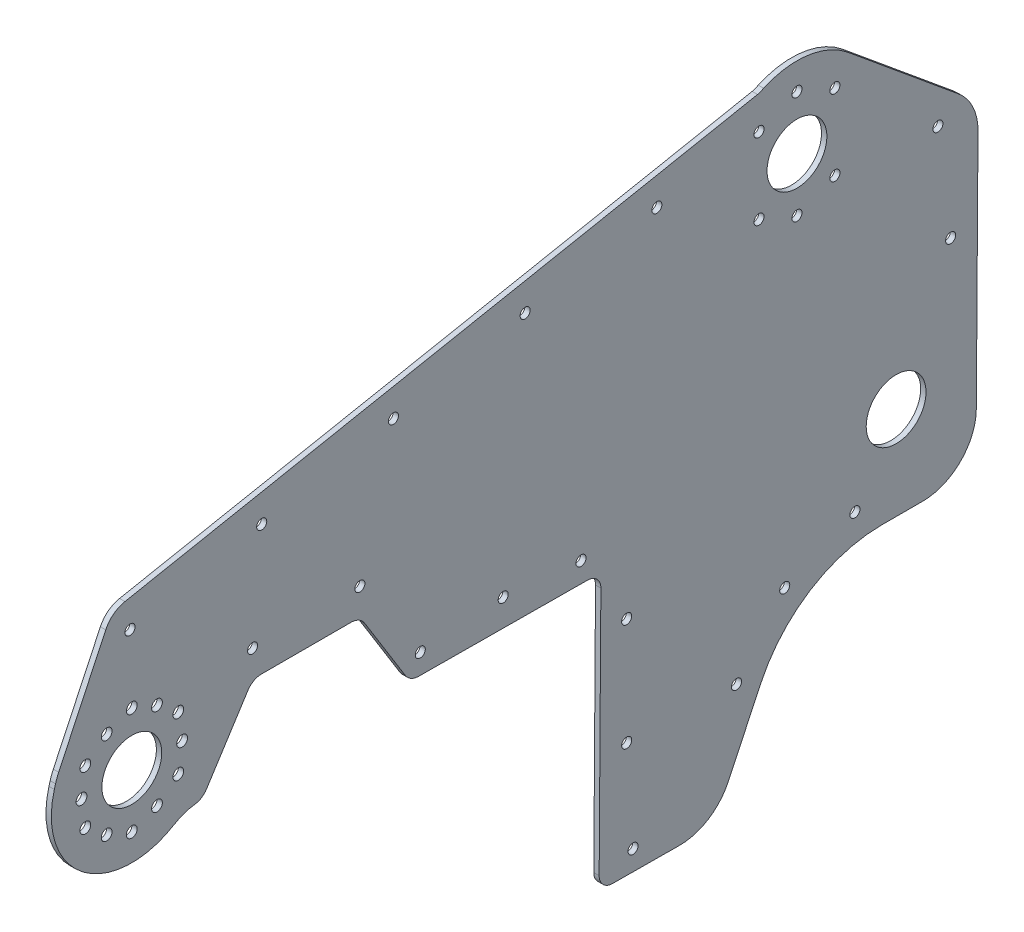
SolidWorks part; units mm, degrees
ref_plane "Front Plane" through (0, 0, 0) normal (0, 0, 1) x (1, 0, 0)
ref_plane "Top Plane" through (0, 0, 0) normal (0, 1, 0) x (1, 0, 0)
ref_plane "Right Plane" through (0, 0, 0) normal (1, 0, 0) x (0, 0, -1)
sketch "Sketch1" plane through (2085.2745, 0, 0) normal (-1, 0, 0) x (0, 0, 1)
  line L0 (-470.4626, 294.284) -> (-813.3543, 291.9025) construction
  line L1 (-819.6601, 285.5085) -> (-816.3083, -197.0799) construction
  line L2 (-816.3083, -197.0799) -> (-644.8624, -195.8891) construction
  line L3 (-638.5567, -189.4951) -> (-639.3726, -72.023) construction
  line L4 (-633.0668, -65.629) -> (-442.3722, -64.3046) construction
  line L5 (-380.6906, -25.2502) -> (-470.4626, 294.284) construction
  line L6 (-470.4626, 294.284) -> (-813.3543, 291.9025) construction
  line L7 (-819.6601, 285.5085) -> (-818.6898, 145.8119) construction
  line L8 (-676.4765, -196.1087) -> (-644.8624, -195.8891)
  line L9 (-638.5567, -189.4951) -> (-639.3726, -72.023)
  line L10 (-633.0668, -65.629) -> (-553.1901, -65.0743)
  line L11 (-380.6906, -25.2502) -> (-381.2742, -23.1727)
  line L12 (-406.6004, 23.1935) -> (-802.249, 140.9199) construction
  line L14 (-756.4363, 89.0125) -> (-808.6343, 45.9004)
  line L15 (-817.8587, 26.1401) -> (-817.0703, -87.3715)
  line L16 (-818.5707, 128.6591) -> (-817.9425, 38.2125) construction
  line L17 (-393.1787, 19.1998) -> (-470.4626, 294.284) construction
  line L18 (-699.6149, -181.5678) -> (-715.0401, -148.9488)
  line L19 (-772.4451, -112.5951) -> (-791.6709, -112.5951)
  line L20 (-816.8951, -112.5951) -> (-816.3083, -197.0799) construction
  line L21 (-816.3083, -197.0799) -> (-692.6854, -196.2212) construction
  line L22 (-530.97, 35.9025) -> (-713.5248, 93.2198) construction
  line L23 (-384.9948, -9.9298) -> (-389.3911, 5.7185) construction
  line L24 (-546.7673, -61.4706) -> (-527.5902, -30.5489)
  line L25 (-521.1144, -26.945) -> (-478.7266, -26.945)
  line L26 (-472.3074, -30.4591) -> (-452.7015, -61.1107)
  line L27 (-405.0283, 28.0353) -> (-382.753, -19.2109)
  line L28 (-475.9205, -39.5052) -> (-523.9205, -39.5052) construction
  line L29 (-475.9205, -39.5052) -> (-523.9205, -39.5052) construction
  line L30 (-548.9841, -65.045) -> (-450.6219, -64.3619) construction
  line L31 (-527.1657, 35.3193) -> (-416.5156, 35.3193) construction
  line L32 (-398.1188, -5.8092) -> (-529.1126, 35.3193) construction
  line L33 (-713.5248, 93.2198) -> (-414.0951, 35.0865)
  line L34 (-792.0032, 59.6366) -> (-540.5464, 59.6366) construction
  arc A0 (-813.3543, 291.9025) -> (-819.6601, 285.5085) centre (-813.3102, 285.5526) ccw construction
  arc A1 (-644.8624, -195.8891) -> (-638.5567, -189.4951) centre (-644.9065, -189.5392) ccw construction
  arc A2 (-633.0668, -65.629) -> (-639.3726, -72.023) centre (-633.0227, -71.9789) ccw construction
  arc A3 (-442.3722, -64.3046) -> (-380.6906, -25.2502) centre (-417.3705, -35.5552) ccw construction
  arc A4 (-813.3543, 291.9025) -> (-819.6601, 285.5085) centre (-813.3102, 285.5526) ccw construction
  arc A5 (-644.8624, -195.8891) -> (-638.5567, -189.4951) centre (-644.9065, -189.5392) ccw
  arc A6 (-633.0668, -65.629) -> (-639.3726, -72.023) centre (-633.0227, -71.9789) ccw
  arc A7 (-437.2155, -68.0789) -> (-380.6906, -25.2502) centre (-417.3705, -35.5552) ccw
  arc A8 (-406.6004, 23.1935) -> (-389.3911, 5.7185) centre (-413.8444, -1.1516) cw construction
  arc A11 (-715.0401, -148.9488) -> (-772.4451, -112.5951) centre (-772.4451, -176.0951) ccw
  arc A12 (-699.6149, -181.5678) -> (-676.4765, -196.1087) centre (-676.6529, -170.7093) ccw
  arc A13 (-791.6709, -112.5951) -> (-817.0703, -87.3715) centre (-791.6709, -87.1951) cw
  arc A14 (-802.249, 140.9199) -> (-818.5707, 128.6591) centre (-805.871, 128.7473) ccw construction
  circle A16 centre (-732.1738, 59.6366) radius 14.1605
  circle A17 centre (-779.0999, -68.5703) radius 14.1605
  circle A18 centre (-654.5854, -186.4314) radius 2.3812
  circle A19 centre (-629.9581, -56.0822) radius 2.3812
  circle A20 centre (-553.8955, -55.5539) radius 2.3812
  circle A21 centre (-417.3705, -35.5552) radius 14.1605
  arc A22 (-716.4192, 94.3267) -> (-756.4363, 89.0125) centre (-732.1738, 59.6366) ccw
  arc A23 (-382.753, -19.2109) -> (-381.2742, -23.1727) centre (-405.7275, -30.0428) cw
  arc A24 (-713.5248, 93.2198) -> (-716.4192, 94.3267) centre (-705.9161, 117.4534) cw
  arc A25 (-808.6343, 45.9004) -> (-817.8587, 26.1401) centre (-792.4593, 26.3165) ccw
  arc A26 (-447.2431, -64.564) -> (-437.2155, -68.0789) centre (-450.4455, -89.7613) cw
  arc A27 (-452.7015, -61.1107) -> (-447.2431, -64.564) centre (-446.2823, -57.0048) ccw
  arc A28 (-546.7673, -61.4706) -> (-553.1901, -65.0743) centre (-553.243, -57.4544) cw
  arc A29 (-478.7266, -26.945) -> (-472.3074, -30.4591) centre (-478.7266, -34.565) cw
  arc A30 (-527.5902, -30.5489) -> (-521.1144, -26.945) centre (-521.1144, -34.565) cw
  arc A31 (-398.1188, -5.8092) -> (-382.753, -19.2109) centre (-405.7275, -30.0428) cw construction
  arc A32 (-527.1657, 35.3193) -> (-530.97, 35.9025) centre (-527.1657, 48.0193) cw construction
  arc A33 (-414.0951, 35.0865) -> (-405.0283, 28.0353) centre (-416.5156, 22.6193) cw
  arc A34 (-416.5156, 35.3193) -> (-414.0951, 35.0865) centre (-416.5156, 22.6193) cw construction
  point P63 (-715.1948, 93.7441)
  point P77 (-499.9205, -26.945)
  point P78 (-499.9205, -39.5052)
  point P87 (-474.5551, -26.945)
  point P90 (-525.3551, -26.945)
  point P96 (-408.4626, 35.3193)
  dimension "D5" = 25.4
  dimension "D8" = 63.5
  dimension "D10" = 25.4
  dimension "D3" = 12.7
  dimension "D4" = 28.321
  dimension "D11" = 38.1
  dimension "D15" = 25.4
  dimension "D16" = 25.4
  dimension "D19" = 7.62
  dimension "D22" = 12.7
  dimension "D23" = 4.7625
  dimension "D1" = 44.45
  dimension "D2" = 146.05
  dimension "D6" = 44.45
  dimension "D7" = 38.1
  dimension "D9" = 76.2
  dimension "D12" = 50.8
  dimension "D13" = 330.2
  dimension "D14" = 53.975
  dimension "D17" = 50.8
  dimension "D18" = 38.1
  dimension "D20" = 60.287
  dimension "D21" = 120.65
  dimension "D24" = 172.2317
  dimension "D25" = 136.525
extrude "Boss-Extrude2" add sketch "Sketch1" along normal blind 2.54
sketch "Sketch2" plane through (2085.2745, 0, 0) normal (1, 0, 0) x (0, 0, -1)
  circle A0 centre (732.1738, 59.6366) radius 14.1605 construction
  circle A1 centre (732.1738, 59.6366) radius 14.1605 construction
  circle A2 centre (732.1738, 85.0366) radius 2.3812
  circle A3 centre (732.1738, 34.2366) radius 2.3812
  circle A4 centre (750.1343, 41.676) radius 2.3812
  circle A5 centre (714.2134, 77.5972) radius 2.3812
  circle A6 centre (732.1738, 59.6366) radius 25.4 construction
  circle A7 centre (750.1343, 77.5972) radius 2.3812
  circle A8 centre (714.2134, 41.676) radius 2.3812
  dimension "D1" = 50.8
  dimension "D2" = 4.7625
  dimension "D3" = 7.4394
  dimension "D4" = 7.4394
extrude "Cut-Extrude1" cut sketch "Sketch2" against normal through all
sketch "Sketch3" plane through (2085.2745, 0, 0) normal (1, 0, 0) x (0, 0, -1)
  circle A1 centre (759.6181, -100.9825) radius 2.3813
  circle A2 centre (759.6181, -100.9825) radius 2.3813
  circle A3 centre (541.1877, 46.532) radius 2.3813
  circle A4 centre (541.1877, 46.532) radius 2.3812
  circle A5 centre (478.8516, 34.4297) radius 2.3813
  circle A6 centre (478.8516, 34.4297) radius 2.3813
  circle A7 centre (416.5156, 22.3274) radius 2.3813
  circle A8 centre (416.5156, 22.3274) radius 2.3813
  circle A9 centre (525.3205, -14.245) radius 2.3813
  circle A10 centre (525.3205, -14.245) radius 2.3813
  circle A11 centre (798.8869, 37.4794) radius 2.3813
  circle A12 centre (798.8869, 37.4794) radius 2.3813
  circle A13 centre (665.8598, 70.7367) radius 2.3813
  circle A14 centre (665.8598, 70.7367) radius 2.3812
  circle A15 centre (603.5237, 58.6344) radius 2.3813
  circle A16 centre (603.5237, 58.6344) radius 2.3812
  circle A17 centre (703.5591, -143.5195) radius 2.3813
  circle A18 centre (703.5591, -143.5195) radius 2.3813
  circle A19 centre (726.3842, -115.3922) radius 2.3813
  circle A20 centre (726.3842, -115.3922) radius 2.3813
  circle A21 centre (804.8987, -11.2496) radius 2.3813
  circle A22 centre (804.8987, -11.2496) radius 2.3813
  circle A23 centre (474.5205, -14.245) radius 2.3813
  circle A24 centre (474.5205, -14.245) radius 2.3813
  circle A25 centre (651.59, -141.5513) radius 2.3813
  circle A26 centre (651.59, -141.5513) radius 2.3813
  circle A27 centre (651.59, -90.7513) radius 2.3813
  circle A28 centre (651.59, -90.7513) radius 2.3813
  circle A29 centre (593.1285, -52.6513) radius 2.3813
  circle A30 centre (593.1285, -52.6513) radius 2.3813
  dimension "D1" = 0
  dimension "D2" = 0
  dimension "D3" = 0
  dimension "D4" = 0
  dimension "D5" = 0
  dimension "D6" = 0
  dimension "D7" = 0
  dimension "D8" = 0
  dimension "D9" = 0
  dimension "D10" = 0
  dimension "D11" = 0
  dimension "D12" = 0
  dimension "D13" = 0
  dimension "D14" = 0
  dimension "D15" = 0
extrude "Cut-Extrude2" cut sketch "Sketch3" against normal up to surface (2.54 mm away) up to face at (2082.7345, 85.0366, -734.5551)
sketch "Sketch4" plane through (2085.2745, 0, 0) normal (1, 0, 0) x (0, 0, -1)
  circle A0 centre (417.3705, -35.5552) radius 14.1605 construction
  circle A1 centre (417.3705, -35.5552) radius 14.1605 construction
sketch "Sketch5" plane through (2085.2745, 0, 0) normal (1, 0, 0) x (0, 0, -1)
  line L0 (-4.7879, -2.7643) -> (0, -5.5286)
  line L1 (0, -5.5286) -> (4.7879, -2.7643)
  line L2 (4.7879, -2.7643) -> (4.7879, 2.7643)
  line L3 (4.7879, 2.7643) -> (0, 5.5286)
  line L4 (0, 5.5286) -> (-4.7879, 2.7643)
  line L5 (-4.7879, 2.7643) -> (-4.7879, -2.7643)
  circle A0 centre (-11.9062, 20.6222) radius 2.5527
  circle A1 centre (0, 25.4) radius 2.5527
  circle A2 centre (-23.8125, 0) radius 2.5527
  circle A3 centre (-21.997, 12.7) radius 2.5527
  circle A4 centre (-11.9062, -20.6222) radius 2.5527
  circle A5 centre (-21.997, -12.7) radius 2.5527
  circle A6 centre (11.9062, -20.6222) radius 2.5527
  circle A7 centre (0, -25.4) radius 2.5527
  circle A8 centre (23.8125, 0) radius 2.5527
  circle A9 centre (21.997, -12.7) radius 2.5527
  circle A10 centre (11.9062, 20.6222) radius 2.5527
  circle A11 centre (21.997, 12.7) radius 2.5527
  circle A12 centre (0, 0) radius 30.1625
sketch "Sketch6" plane through (2085.2745, 0, 0) normal (1, 0, 0) x (0, 0, -1)
  line L0 (405.4643, -14.933) -> (393.558, -35.5552) construction
  line L1 (393.558, -35.5552) -> (405.4643, -56.1775) construction
  line L2 (405.4643, -56.1775) -> (429.2768, -56.1775) construction
  line L3 (429.2768, -56.1775) -> (441.183, -35.5552) construction
  line L4 (441.183, -35.5552) -> (429.2768, -14.933) construction
  line L5 (429.2768, -14.933) -> (405.4643, -14.933) construction
  line L6 (395.3735, -22.8552) -> (417.3705, -10.1552) construction
  line L7 (417.3705, -10.1552) -> (439.3675, -22.8552) construction
  line L8 (439.3675, -22.8552) -> (439.3675, -48.2552) construction
  line L9 (439.3675, -48.2552) -> (417.3705, -60.9552) construction
  line L10 (417.3705, -60.9552) -> (395.3735, -48.2552) construction
  line L11 (395.3735, -48.2552) -> (395.3735, -22.8552) construction
  circle A0 centre (417.3705, -35.5552) radius 23.8125 construction
  circle A1 centre (417.3705, -35.5552) radius 25.4 construction
  circle A2 centre (395.3735, -48.2552) radius 2.5527
  circle A3 centre (417.3705, -35.5552) radius 14.1605 construction
  circle A4 centre (405.4643, -56.1775) radius 2.5527
  circle A6 centre (395.3735, -22.8552) radius 2.5527
  circle A8 centre (393.558, -35.5552) radius 2.5527
  circle A10 centre (417.3705, -10.1552) radius 2.5527
  circle A12 centre (405.4643, -14.933) radius 2.5527
  circle A14 centre (439.3675, -22.8552) radius 2.5527
  circle A16 centre (429.2768, -14.933) radius 2.5527
  circle A18 centre (439.3675, -48.2552) radius 2.5527
  circle A20 centre (441.183, -35.5552) radius 2.5527
  circle A22 centre (417.3705, -60.9552) radius 2.5527
  circle A24 centre (429.2768, -56.1775) radius 2.5527
  point P0 (417.2615, -35.4276)
  point P6 (351.2352, -23.2405)
  point P9 (338.8998, -30.598)
  dimension "D1" = 50.8
  dimension "D2" = 47.625
  dimension "D3" = 5.1054
extrude "Cut-Extrude3" cut sketch "Sketch6" against normal through all
